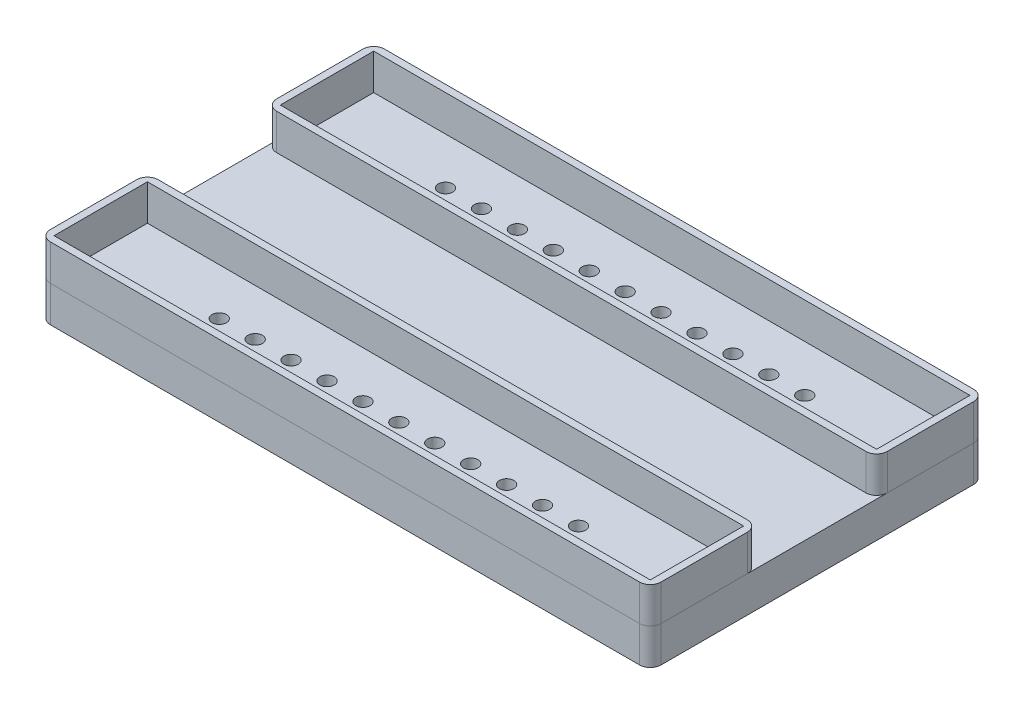
SolidWorks part; units mm, degrees
ref_plane "前视基准面" through (0, 0, 0) normal (0, 0, 1) x (1, 0, 0)
ref_plane "上视基准面" through (0, 0, 0) normal (0, 1, 0) x (1, 0, 0)
ref_plane "右视基准面" through (0, 0, 0) normal (1, 0, 0) x (0, 0, -1)
sketch "草图1" plane through (0, 0, 0) normal (0, 1, 0) x (1, 0, 0)
  line L1 (-85, 46.5) -> (85, 46.5)
  line L2 (-85, 46.5) -> (-85, -46.5)
  line L3 (-85, -46.5) -> (85, -46.5)
  line L4 (85, 46.5) -> (85, -46.5)
  line L5 (0, -46.5) -> (0, 46.5) construction
  line L6 (-85, 0) -> (85, 0) construction
  point P0 (0, 0)
  dimension "D1" = 93
  dimension "D2" = 170
extrude "凸台-拉伸1" add sketch "草图1" along normal blind 10
sketch "草图2" plane through (0, 10, 0) normal (0, 1, 0) x (1, 0, 0)
  line L0 (85, 46.5) -> (-85, 46.5) construction
  line L1 (-85, 46.5) -> (85, 46.5)
  line L2 (-85, 46.5) -> (-85, 16.5)
  line L3 (-85, 16.5) -> (85, 16.5)
  line L4 (85, 46.5) -> (85, 16.5)
  line L5 (-85, 46.5) -> (-85, -46.5) construction
  line L6 (85, -46.5) -> (85, 46.5) construction
  line L7 (-83, 44.5) -> (-83, 18.5)
  line L8 (-83, 18.5) -> (83, 18.5)
  line L9 (83, 44.5) -> (83, 18.5)
  line L10 (-83, 44.5) -> (83, 44.5)
  line L11 (-85, 0) -> (85, 0) construction
  line L12 (-85, 0) -> (85, 0) construction
  line L13 (0, -46.5) -> (0, 46.5) construction
  line L14 (-83, -44.5) -> (83, -44.5)
  line L15 (83, -44.5) -> (83, -18.5)
  line L16 (-83, -18.5) -> (83, -18.5)
  line L17 (-83, -44.5) -> (-83, -18.5)
  line L18 (-85, -16.5) -> (85, -16.5)
  line L19 (85, -46.5) -> (85, -16.5)
  line L20 (-85, -46.5) -> (85, -46.5)
  line L21 (-85, -46.5) -> (-85, -16.5)
  line L23 (-83, 31.5) -> (85, 31.5) construction
  circle A0 centre (0, 31.5) radius 2
  circle A1 centre (10, 31.5) radius 2
  circle A2 centre (20, 31.5) radius 2
  circle A3 centre (30, 31.5) radius 2
  circle A4 centre (40, 31.5) radius 2
  circle A5 centre (50, 31.5) radius 2
  circle A6 centre (-10, 31.5) radius 2
  circle A7 centre (-20, 31.5) radius 2
  circle A8 centre (-30, 31.5) radius 2
  circle A9 centre (-40, 31.5) radius 2
  circle A10 centre (-50, 31.5) radius 2
  circle A11 centre (50, -31.5) radius 2
  circle A12 centre (40, -31.5) radius 2
  circle A13 centre (30, -31.5) radius 2
  circle A14 centre (20, -31.5) radius 2
  circle A15 centre (10, -31.5) radius 2
  circle A16 centre (0, -31.5) radius 2
  circle A17 centre (-10, -31.5) radius 2
  circle A18 centre (-20, -31.5) radius 2
  circle A19 centre (-30, -31.5) radius 2
  circle A20 centre (-40, -31.5) radius 2
  circle A21 centre (-50, -31.5) radius 2
  point P30 (0, 31.5)
  point P75 (0, 0)
  line M9 (85, -46.5) -> (85, 46.5)
  line M10 (85, 46.5) -> (-85, 46.5)
  line M11 (-85, 46.5) -> (-85, -46.5)
  line M12 (-85, -46.5) -> (85, -46.5)
  dimension "D4" = 4
  dimension "D1" = 30
  dimension "D3" = 6
  dimension "D6" = 93
  dimension "D2" = 2
  dimension "D5" = 6
ref_axis "基准轴1" through (-85, 0, 0) along (1, 0, 0)
extrude "凸台-拉伸2" add sketch "草图2" along normal blind 10 separate body contours L3 L7 L10 L9 L8 M11 M9 M10 | L18 L14 L17 L16 L15 M11 M12 M9 region at (0, 10, -44.7737) region at (0, 10, 18.2263)
extrude "切除-拉伸2" cut sketch "草图2<4>" against normal blind 5 contours A11 | A12 | A13 | A14 | A15 | A16 | A19 | A20 | A21 | A5 | A4 | A3 | A2 | A1 | A0 | A6 | A7 | A8 | A9 | A10 | A17 | A18 region at (0, 10, -31.5) region at (10, 10, -31.5) region at (20, 10, -31.5) region at (30, 10, -31.5) region at (40, 10, -31.5) region at (50, 10, -31.5) region at (-10, 10, -31.5) region at (-20, 10, -31.5) region at (-30, 10, -31.5) region at (-40, 10, -31.5) region at (-50, 10, -31.5) region at (50, 10, 31.5) region at (40, 10, 31.5) region at (30, 10, 31.5) region at (20, 10, 31.5) region at (10, 10, 31.5) region at (0, 10, 31.5) region at (-30, 10, 31.5) region at (-40, 10, 31.5) region at (-50, 10, 31.5)
sketch "草图2<4>" plane through (0, 10, 0) normal (0, 1, 0) x (1, 0, 0) same geometry as "草图2"
fillet "圆角2" radius 3 4 edges at (-85, 15, -46.5) (85, 15, -46.5) (85, 15, -16.5) (-85, 15, -16.5)
fillet "圆角3" radius 3 4 edges at (85, 15, 46.5) (-85, 15, 46.5) (-85, 15, 16.5) (85, 15, 16.5)
fillet "圆角4" radius 3 4 edges at (85, 5, 46.5) (-85, 5, 46.5) (-85, 5, -46.5) (85, 5, -46.5)
